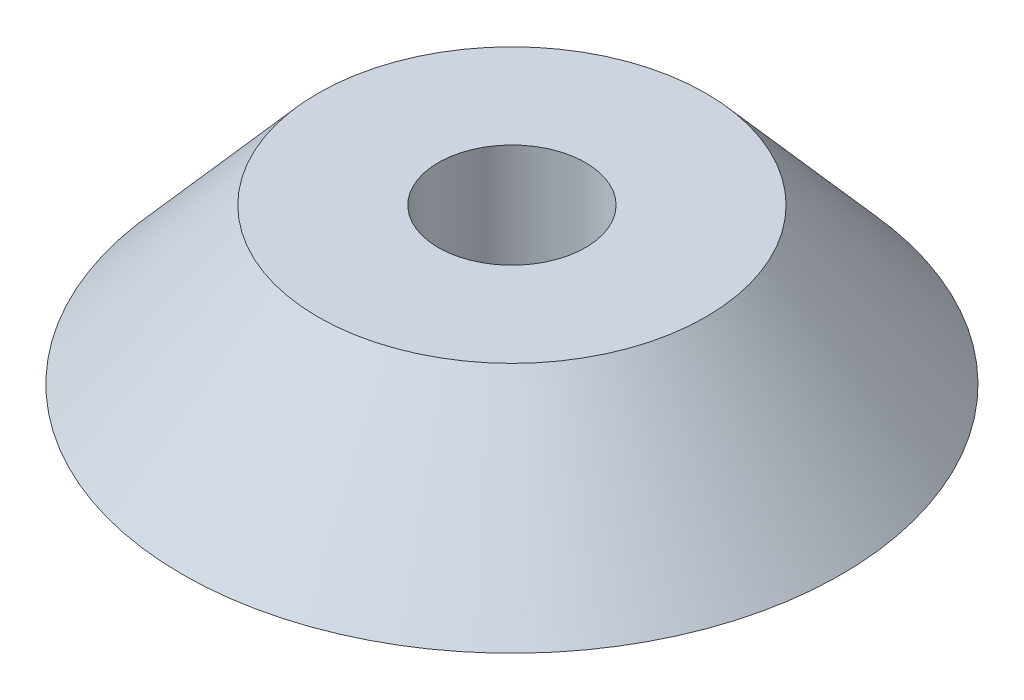
SolidWorks part; units mm, degrees
ref_plane "Front" through (0, 0, 0) normal (0, 0, 1) x (1, 0, 0)
ref_plane "Top" through (0, 0, 0) normal (0, 1, 0) x (1, 0, 0)
ref_plane "Right" through (0, 0, 0) normal (1, 0, 0) x (0, 0, -1)
sketch "Sketch1" plane through (0, 0, 0) normal (0, 1, 0) x (1, 0, 0)
  circle A0 centre (0, 0) radius 2.413
  circle A1 centre (0, 0) radius 10.795
  dimension "D1" = 21.59
  dimension "D2" = 4.826
ref_plane "Plane1" through (0, 5.08, 0) normal (0, 1, 0) x (1, 0, 0)
sketch "Sketch2" plane through (0, 5.08, 0) normal (0, 1, 0) x (1, 0, 0)
  circle A0 centre (0, 0) radius 2.413
  circle A1 centre (0, 0) radius 6.35
  dimension "D1" = 12.7
  dimension "D2" = 4.826
loft "Loft1" add section "Sketch1" section "Sketch2" connector at (-8.6081, 0, 6.514) connector at (-4.4362, 5.08, 4.5434)
extrude "Cut-Extrude1" cut sketch "Sketch1<3>" along normal through all contours A0 region at (0, 0, 0)
sketch "Sketch1<3>" plane through (0, 0, 0) normal (0, 1, 0) x (1, 0, 0) same geometry as "Sketch1"
